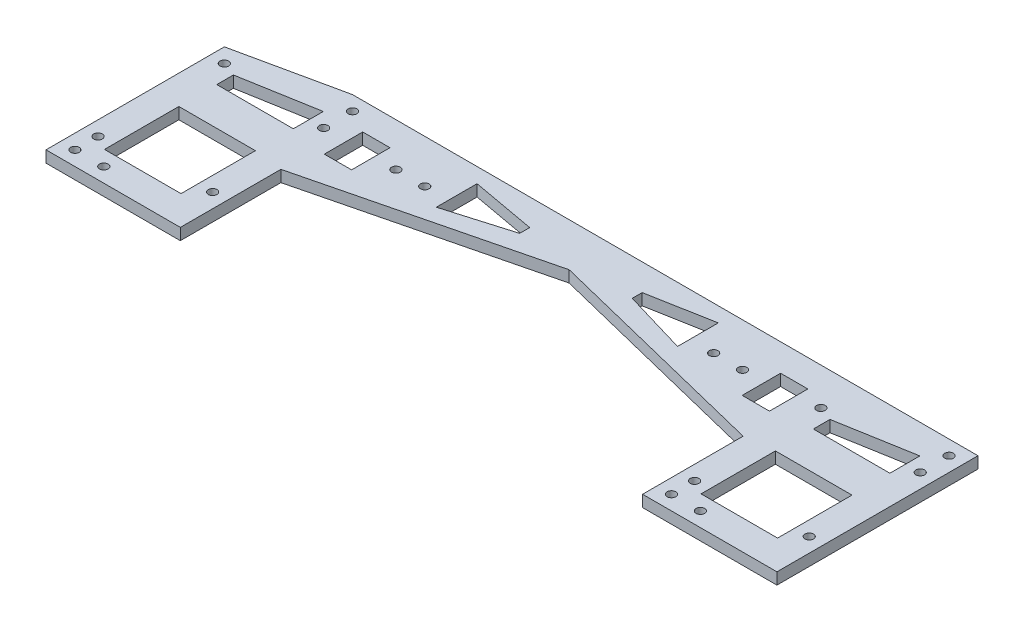
SolidWorks part; units mm, degrees
ref_plane "Front Plane" through (0, 0, 0) normal (0, 0, 1) x (1, 0, 0)
ref_plane "Top Plane" through (0, 0, 0) normal (0, 1, 0) x (1, 0, 0)
ref_plane "Right Plane" through (0, 0, 0) normal (1, 0, 0) x (0, 0, -1)
sketch "Sketch1" plane through (0, 0, 0) normal (0, 1, 0) x (1, 0, 0)
  line L0 (0, 0) -> (0, 10.18) construction
  line L1 (0, 10.18) -> (36.5, 10.18) construction
  line L2 (0, 0) -> (0, 51.73) construction
  line L3 (36.5, 10.18) -> (36.5, 49.6) construction
  line L4 (36.5, 49.6) -> (36.5, 59.6) construction
  line L5 (0, 0) -> (0, -5) construction
  line L6 (5, -5) -> (-5, -5)
  line L7 (0, 51.73) -> (0, 56.73) construction
  line L8 (5, 56.73) -> (-5, 56.73)
  line L9 (-5, 56.73) -> (-5, -5)
  line L10 (5, 56.73) -> (5, -5)
  line L11 (36.5, 59.6) -> (36.5, 64.6) construction
  line L12 (41.5, 64.6) -> (31.5, 64.6)
  line L13 (36.5, 10.18) -> (36.5, -19.82) construction
  line L14 (41.5, -19.82) -> (31.5, -19.82)
  line L15 (31.5, 64.6) -> (31.5, -19.82)
  line L16 (41.5, 64.6) -> (41.5, -19.82)
  line L17 (31.5, 64.6) -> (-5, 56.73)
  line L18 (5, 56.73) -> (31.5, 54.48)
  line L19 (5, -5) -> (31.5, -5)
  line L20 (5, 5.234) -> (31.5, 5.234)
  line L21 (31.5, -5) -> (41.5, -5)
  line L22 (36.5, 10.18) -> (38.7718, 10.18) construction
  line L23 (38.7718, 10.18) -> (38.7718, 11.18) construction
  line L24 (38.7718, 11.18) -> (36.5, 11.18) construction
  circle A0 centre (0, 0) radius 1.5
  circle A2 centre (0, 51.73) radius 1.5
  circle A3 centre (36.5, 49.6) radius 1.5
  circle A4 centre (36.5, 59.6) radius 1.5
  circle A5 centre (36.5, 11.18) radius 1.5
  dimension "D1" = 10.18
  dimension "D2" = 36.5
  dimension "D3" = 51.73
  dimension "D4" = 39.42
  dimension "D5" = 10
  dimension "D6" = 5
  dimension "D7" = 5
  dimension "D8" = 5
  dimension "D9" = 5
  dimension "D10" = 5
  dimension "D11" = 5
  dimension "D12" = 1
extrude "Boss-Extrude1" add sketch "Sketch1" along normal blind 3 contours L16 L12 L15 L14 A4 A3 A5 | L8 L18 L15 L17 | L10 L8 L9 L6 A2 A0 | L10 L14 L15 region at (0, 0, -25.865) region at (18.25, 0, -0.117) region at (36.5, 0, -29.4755) region at (19.9063, 0, -58.7735)
sketch "Sketch2" plane through (0, 3, 0) normal (0, 1, 0) x (1, 0, 0)
  line L0 (5, 44.1091) -> (31.5, 44.1091)
  line L1 (5, 56.73) -> (5, 5.234) construction
  line L2 (31.5, 54.48) -> (31.5, 5.234) construction
  line L3 (31.5, 44.1091) -> (31.5, 30.982)
  line L4 (31.5, 30.982) -> (5, 30.982)
  line L5 (5, 30.982) -> (5, 44.1091)
  line L6 (5, 56.73) -> (5, 49.8671)
  line L7 (5, 56.73) -> (5, 5.234) construction
  line L8 (5, 49.8671) -> (31.5, 54.48)
  line L9 (31.5, 54.48) -> (5, 56.73)
extrude "Boss-Extrude2" add sketch "Sketch2" against normal blind 3
sketch "Sketch3" plane through (0, 3, 0) normal (0, 1, 0) x (1, 0, 0)
  line L0 (0, 0) -> (10, 0) construction
  circle A0 centre (10, 0) radius 1.5
  dimension "D1" = 10
extrude "Cut-Extrude1" cut sketch "Sketch3" against normal blind 10
sketch "Sketch4" plane through (0, 3, 0) normal (0, 1, 0) x (1, 0, 0)
  line L0 (0, 0) -> (0, 8) construction
  circle A0 centre (0, 8) radius 1.5
extrude "Cut-Extrude2" cut sketch "Sketch4" against normal blind 10
sketch "Sketch6" plane through (0, 3, 0) normal (0, 1, 0) x (1, 0, 0)
  line L0 (-5, 56.73) -> (-5, -5)
  line L1 (-5, -5) -> (41.5, -5)
  line L2 (41.5, -5) -> (41.5, 64.6)
  line L3 (41.5, 64.6) -> (31.5, 64.6)
  line L4 (31.5, 64.6) -> (-5, 56.73)
  line L5 (41.5, 29.8) -> (41.5, 64.6) construction
  line L6 (41.5, 29.8) -> (201.5, 29.8) construction
  line L7 (5, 30.982) -> (5, 5.234)
  line L8 (5, 5.234) -> (31.5, 5.234)
  line L9 (31.5, 5.234) -> (31.5, 30.982)
  line L10 (31.5, 30.982) -> (5, 30.982)
  line L11 (5, 44.1091) -> (5, 49.8671)
  line L12 (5, 49.8671) -> (31.5, 54.48)
  line L13 (31.5, 54.48) -> (31.5, 44.1091)
  line L14 (31.5, 44.1091) -> (5, 44.1091)
  line L15 (201.5, 56.73) -> (201.5, -5)
  line L16 (201.5, -5) -> (248, -5)
  line L17 (248, -5) -> (248, 64.6)
  line L18 (248, 64.6) -> (238, 64.6)
  line L19 (238, 64.6) -> (201.5, 56.73)
  line L20 (211.5, 30.982) -> (211.5, 5.234)
  line L21 (211.5, 5.234) -> (238, 5.234)
  line L22 (238, 5.234) -> (238, 30.982)
  line L23 (238, 30.982) -> (211.5, 30.982)
  line L24 (211.5, 44.1091) -> (211.5, 49.8671)
  line L25 (211.5, 49.8671) -> (238, 54.48)
  line L26 (238, 54.48) -> (238, 44.1091)
  line L27 (238, 44.1091) -> (211.5, 44.1091)
  line L28 (248, 29.8) -> (248, 64.6) construction
  line L29 (248, 64.6) -> (238, 64.6)
  line L30 (41.5, 64.6) -> (248, 64.6)
  line L31 (121.5, 29.8) -> (121.5, -34.9935) construction
  line L32 (41.5, 29.8) -> (121.5, 49.6)
  line L33 (121.5, 49.6) -> (201.5, 29.8)
  circle A0 centre (0, 51.73) radius 1.5
  circle A1 centre (36.5, 59.6) radius 1.5
  circle A2 centre (36.5, 49.6) radius 1.5
  circle A3 centre (36.5, 11.18) radius 1.5
  circle A4 centre (10, 0) radius 1.5
  circle A5 centre (0, 0) radius 1.5
  circle A6 centre (0, 8) radius 1.5
  circle A7 centre (206.5, 51.73) radius 1.5
  circle A8 centre (243, 59.6) radius 1.5
  circle A9 centre (243, 49.6) radius 1.5
  circle A10 centre (243, 11.18) radius 1.5
  circle A11 centre (216.5, 0) radius 1.5
  circle A12 centre (206.5, 0) radius 1.5
  circle A13 centre (206.5, 8) radius 1.5
  circle M6 centre (0, 8) radius 1.5
  circle M7 centre (10, 0) radius 1.5
  line M8 (5, 49.8671) -> (31.5, 54.48)
  line M9 (31.5, 54.48) -> (31.5, 44.1091)
  line M10 (31.5, 44.1091) -> (5, 44.1091)
  line M11 (5, 44.1091) -> (5, 49.8671)
  line M12 (5, 5.234) -> (5, 30.982)
  line M13 (5, 30.982) -> (31.5, 30.982)
  line M14 (31.5, 30.982) -> (31.5, 5.234)
  line M15 (31.5, 5.234) -> (5, 5.234)
  line M16 (-5, 56.73) -> (-5, -5)
  line M17 (-5, -5) -> (41.5, -5)
  line M18 (41.5, -5) -> (41.5, 64.6)
  line M19 (41.5, 64.6) -> (31.5, 64.6)
  line M20 (31.5, 64.6) -> (-5, 56.73)
  circle M21 centre (36.5, 11.18) radius 1.5
  circle M22 centre (36.5, 59.6) radius 1.5
  circle M23 centre (36.5, 49.6) radius 1.5
  circle M24 centre (0, 51.73) radius 1.5
  circle M25 centre (0, 0) radius 1.5
  dimension "D1" = 160
  dimension "D2" = 2
extrude "Boss-Extrude4" add sketch "Sketch6" against normal blind 4 contours L32 L33 L15 L19 L30 L2 | L2 M20 M16 M17 M18 M19 M7 M21 M23 M25 M24 M22 M15 M12 M13 M14 M11 M8 M9 M10 M6 | L18 L19 L15 L16 L17 A13 A12 A11 A10 A9 A8 A7 L23 L22 L21 L20 L26 L27 L24 L25 region at (13.4264, 3, -59.8468) region at (124.7071, 3, -51.8587) region at (243, 3, -63.763)
sketch "Sketch8" plane through (0, -1, 0) normal (0, -1, 0) x (1, 0, 0)
  line L0 (41.5, -29.8) -> (201.5, -29.8) construction
  line L1 (121.5, -49.6) -> (79.7586, -39.269)
  line L2 (41.5, -29.8) -> (121.5, -49.6) construction
  line L3 (79.7586, -39.269) -> (79.7586, -64.6)
  line L4 (31.5, -64.6) -> (248, -64.6) construction
  line L5 (79.7586, -64.6) -> (122.0752, -64.6)
  line L6 (121.5, -49.6) -> (121.5, -55.7806) construction
  line L7 (121.5, -49.6) -> (163.2414, -39.269)
  line L8 (163.2414, -64.6) -> (120.9248, -64.6)
  line L9 (163.2414, -39.269) -> (163.2414, -64.6)
  line L10 (122.0752, -64.6) -> (120.9248, -64.6)
sketch "Sketch9" plane through (0, 3, 0) normal (0, 1, 0) x (1, 0, 0)
  line L0 (36.5, 49.6) -> (61.5, 49.6) construction
  line L1 (121.5, 49.6) -> (121.5, 58.5199) construction
  circle A0 centre (61.5, 49.6) radius 1.5
  circle A1 centre (181.5, 49.6) radius 1.5
  dimension "D1" = 25
extrude "Cut-Extrude3" cut sketch "Sketch9" against normal blind 6
sketch "Sketch10" plane through (0, 3, 0) normal (0, 1, 0) x (1, 0, 0)
  line L0 (121.5, 49.6) -> (121.5, 63.2667) construction
  line L1 (79.7586, 59.4471) -> (79.7586, 45.3542)
  line L2 (79.7586, 39.269) -> (79.7586, 64.6) construction
  line L3 (79.7586, 45.3542) -> (102.0233, 51.9345)
  line L4 (102.0233, 51.9345) -> (102.0233, 55.3991)
  line L5 (102.0233, 55.3991) -> (79.7586, 59.4471)
  line L6 (140.9767, 51.9345) -> (140.9767, 55.3991)
  line L7 (163.2414, 45.3542) -> (140.9767, 51.9345)
  line L8 (163.2414, 59.4471) -> (163.2414, 45.3542)
  line L9 (140.9767, 55.3991) -> (163.2414, 59.4471)
extrude "Cut-Extrude4" cut sketch "Sketch10" against normal blind 14
sketch "Sketch11" plane through (0, 3, 0) normal (0, 1, 0) x (1, 0, 0)
  line L0 (61.5, 49.6) -> (71.5, 49.6) construction
  line L1 (181.5, 49.6) -> (171.5, 49.6) construction
  circle A0 centre (71.5, 49.6) radius 1.5
  circle A1 centre (171.5, 49.6) radius 1.5
  dimension "D2" = 10
  dimension "D1" = 10
extrude "Cut-Extrude5" cut sketch "Sketch11" against normal blind 14
sketch "Sketch12" plane through (0, 3, 0) normal (0, 1, 0) x (1, 0, 0)
  line L0 (121.5, 49.6) -> (121.5, 64.6) construction
  line L1 (79.7586, 64.6) -> (122.0752, 64.6) construction
  line L2 (198.5394, 41.8706) -> (189.1002, 41.8706)
  line L3 (44.4606, 55.1624) -> (53.8998, 55.1624)
  line L4 (44.4606, 55.1624) -> (44.4606, 41.8706)
  line L5 (44.4606, 41.8706) -> (53.8998, 41.8706)
  line L6 (53.8998, 55.1624) -> (53.8998, 41.8706)
  line L7 (189.1002, 55.1624) -> (189.1002, 41.8706)
  line L8 (198.5394, 55.1624) -> (189.1002, 55.1624)
  line L9 (198.5394, 55.1624) -> (198.5394, 41.8706)
extrude "Cut-Extrude6" cut sketch "Sketch12" against normal blind 10
